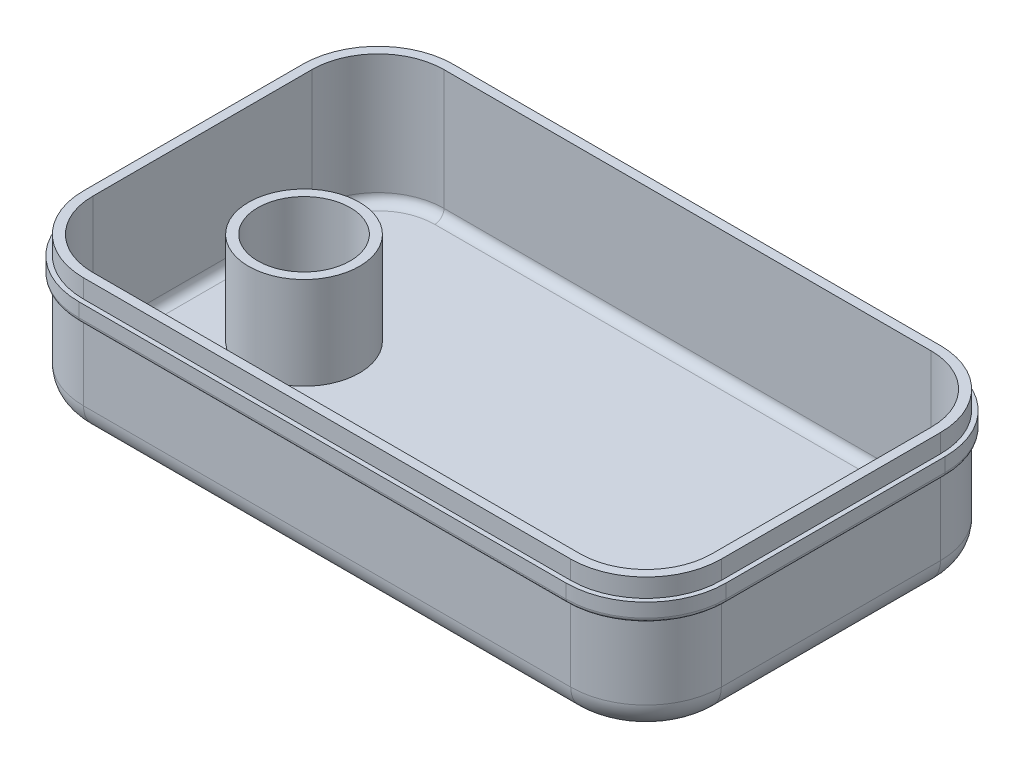
SolidWorks part; units mm, degrees
material "PS Średni/wysoki przepływ"
ref_plane "Płaszczyzna przednia" through (0, 0, 0) normal (0, 0, 1) x (1, 0, 0)
ref_plane "Płaszczyzna górna" through (0, 0, 0) normal (0, 1, 0) x (1, 0, 0)
ref_plane "Płaszczyzna prawa" through (0, 0, 0) normal (1, 0, 0) x (0, 0, -1)
sketch "Szkic1" plane through (0, 0, 0) normal (0, 1, 0) x (1, 0, 0)
  line L0 (0, 0) -> (0, 40) construction
  line L1 (0, 0) -> (-75.5472, 0) construction
  line L2 (-26.3536, 19) -> (26.3536, 19)
  line L3 (-26.3536, 20) -> (26.3536, 20)
  line L4 (-34.5, 11.8536) -> (-34.5, -11.8536)
  line L5 (-26.3536, -20) -> (26.3536, -20)
  line L6 (34.5, 11.8536) -> (34.5, -11.8536)
  line L7 (33.5, 11.8536) -> (33.5, -11.8536)
  line L8 (-26.3536, -19) -> (26.3536, -19)
  line L9 (-33.5, 11.8536) -> (-33.5, -11.8536)
  arc A0 (-26.3536, -20) -> (-34.5, -11.8536) centre (-26.3536, -11.8536) cw
  arc A1 (34.5, -11.8536) -> (26.3536, -20) centre (26.3536, -11.8536) cw
  arc A2 (26.3536, 20) -> (34.5, 11.8536) centre (26.3536, 11.8536) cw
  arc A3 (-26.3536, 20) -> (-34.5, 11.8536) centre (-26.3536, 11.8536) ccw
  arc A4 (26.3536, 19) -> (33.5, 11.8536) centre (26.3536, 11.8536) cw
  arc A5 (33.5, -11.8536) -> (26.3536, -19) centre (26.3536, -11.8536) cw
  arc A6 (-26.3536, -19) -> (-33.5, -11.8536) centre (-26.3536, -11.8536) cw
  arc A7 (-26.3536, 19) -> (-33.5, 11.8536) centre (-26.3536, 11.8536) ccw
  circle A8 centre (-22.5, 0) radius 5
  circle A9 centre (-22.5, 0) radius 6
  point P10 (-34.5, -20)
  point P15 (34.5, 20)
  point P18 (-34.5, 20)
  dimension "D3" = 8.1464
  dimension "D5" = 11
  dimension "D1" = 69
  dimension "D2" = 40
  dimension "D4" = 1
  dimension "D6" = 1
extrude "Dodanie-wyciągnięcie1" add sketch "Szkic1" along normal blind 15 contours A3 L4 A0 L5 A1 L6 A2 L3 | A7 L9 A6 L8 A5 L7 A4 L2
extrude "Dodanie-wyciągnięcie2" add sketch "Szkic1<3>" along normal blind 1 contours L2 A7 L9 A6 L8 A5 L7 A4 A9 region at (1.0651, 0, 0)
sketch "Szkic1<3>" plane through (0, 0, 0) normal (0, 1, 0) x (1, 0, 0) same geometry as "Szkic1"
extrude "Dodanie-wyciągnięcie3" add sketch "Szkic1<4>" along normal blind 11 contours A9 A8 region at (-28.3303, 0, 0)
sketch "Szkic1<4>" plane through (0, 0, 0) normal (0, 1, 0) x (1, 0, 0) same geometry as "Szkic1"
fillet "Zaokrąglenie1" radius 3 8 edges at (-34.5, 0, 0) (-32.114, 0, -17.614) (0, 0, -20) (32.114, 0, -17.614) (34.5, 0, 0) (32.114, 0, 17.614) (-32.114, 0, 17.614) (0, 0, 20)
ref_plane "Płaszczyzna1" through (0, 13, 0) normal (0, 1, 0) x (1, 0, 0)
sketch "Szkic2" plane through (0, 13, 0) normal (0, 1, 0) x (1, 0, 0)
  line L0 (-26.3536, 20) -> (26.3536, 20)
  line L1 (34.5, -11.8536) -> (34.5, 11.8536)
  line L2 (-26.3536, -20) -> (26.3536, -20)
  line L3 (-34.5, 11.8536) -> (-34.5, -11.8536)
  arc A0 (26.3536, 20) -> (34.5, 11.8536) centre (26.3536, 11.8536) cw
  arc A1 (-34.5, 11.8536) -> (-26.3536, 20) centre (-26.3536, 11.8536) cw
  arc A2 (34.5, -11.8536) -> (26.3536, -20) centre (26.3536, -11.8536) cw
  arc A3 (-26.3536, -20) -> (-34.5, -11.8536) centre (-26.3536, -11.8536) cw
sketch "Szkic3" plane through (0, 0, 0) normal (1, 0, 0) x (0, 0, -1)
  line L0 (20, 13) -> (20.5, 13)
  line L1 (20, 13) -> (11.8536, 13) construction
  line L2 (20, 13) -> (11.8536, 13) construction
  line L3 (20.5, 13) -> (20.5, 11.5)
  line L5 (20, 15) -> (20, 3) construction
  line L6 (20, 13) -> (20, 11)
  arc A0 (20, 11) -> (20.5, 11.5) centre (20, 11.5) ccw
  point P12 (20.998, 11.063)
  dimension "D4" = 0.5
  dimension "D1" = 0.5
  dimension "D2" = 2
sweep "Wyciągnięcie po ścieżce1" add profiles "Szkic3" path "Szkic2"
fillet "Zaokrąglenie2" radius 0.5 1 edges at (-22.5, 0, 5)
fillet "Zaokrąglenie3" radius 1 8 edges at (-31.4069, 1, 16.9069) (-33.5, 1, 0) (-31.4069, 1, -16.9069) (0, 1, -19) (31.4069, 1, -16.9069) (33.5, 1, 0) (31.4069, 1, 16.9069) (0, 1, 19)
sketch "Szkic4" [suppressed] plane through (-34.5, 0, 0) normal (-1, 0, 0) x (0, 0, 1)
  line L0 (-11.8536, 7) -> (11.8536, 7) construction
  line L1 (-11.8536, 11) -> (-11.8536, 3) construction
  line L2 (11.8536, 11) -> (11.8536, 3) construction
  line L3 (0, 12.25) -> (0, 7) construction
  line L4 (11.8536, 13) -> (-11.8536, 13) construction
  point P10 (0, 12.25)
  dimension "D1" = 0.75
sketch "Szkic5" [suppressed] plane through (-35, 0, 0) normal (-1, 0, 0) x (0, 0, 1)
  point P0 (0, 12.25)
ref_plane "Płaszczyzna2" through (-35, 0, 0) normal (-1, 0, 0) x (0, 0, 1)
sketch "Szkic6" plane through (-35, 0, 0) normal (-1, 0, 0) x (0, 0, 1)
  line L0 (-11.8536, 7) -> (11.8536, 7) construction
  line L3 (0, 12.25) -> (0, 7) construction
